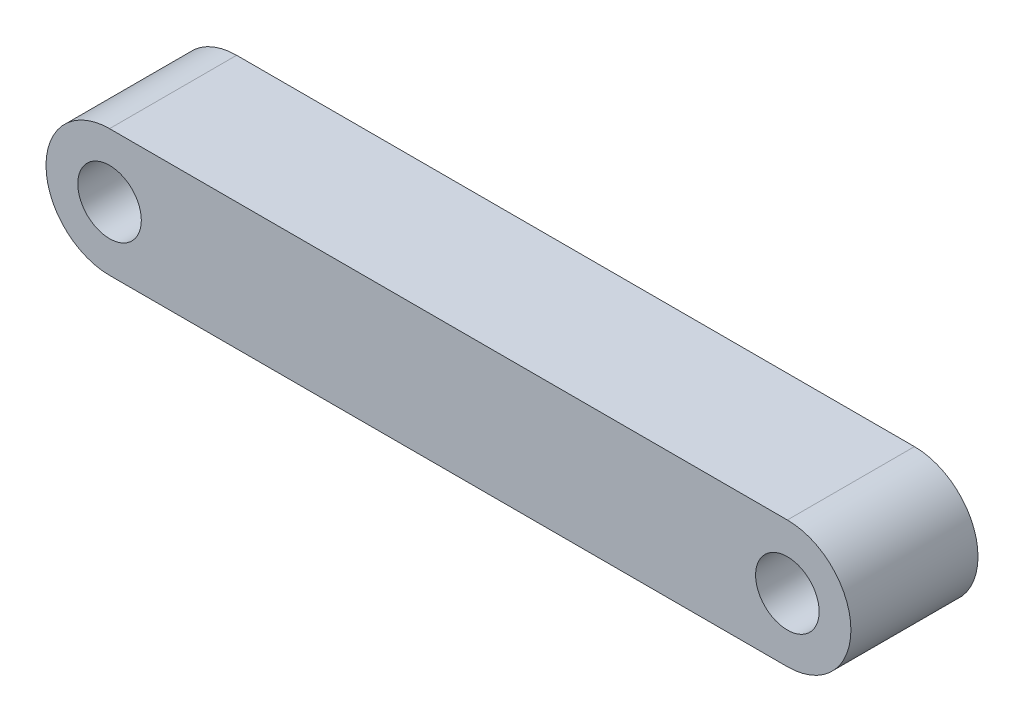
SolidWorks part; units mm, degrees
ref_plane "Plan de face" through (0, 0, 0) normal (0, 0, 1) x (1, 0, 0)
ref_plane "Plan de dessus" through (0, 0, 0) normal (0, 1, 0) x (1, 0, 0)
ref_plane "Plan de droite" through (0, 0, 0) normal (1, 0, 0) x (0, 0, -1)
sketch "Esquisse1" plane through (0, 0, 0) normal (0, 0, 1) x (1, 0, 0)
  line L0 (0, 0) -> (32, 0) construction
  line L1 (0, 3) -> (32, 3)
  line L2 (0, -3) -> (32, -3)
  arc A0 (0, 3) -> (0, -3) centre (0, 0) ccw
  arc A1 (32, -3) -> (32, 3) centre (32, 0) ccw
  circle A2 centre (0, 0) radius 1.5
  circle A3 centre (32, 0) radius 1.5
  point P3 (16, 0)
  dimension "D1" = 3
  dimension "D2" = 6
  dimension "D3" = 32
extrude "Boss.-Extru.1" add sketch "Esquisse1" along normal blind 3 and the other way blind 3
sketch "Esquisse2" plane through (0, 0, 0) normal (0, 0, 1) x (1, 0, 0)
  point P0 (0, 0)
  point P1 (32, 0)
